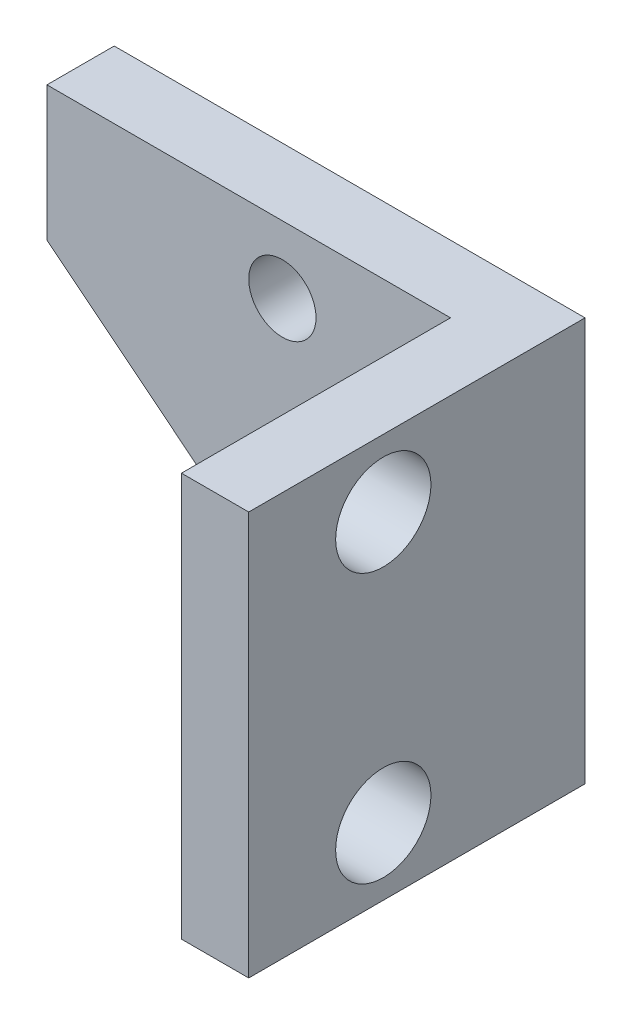
SolidWorks part; units mm, degrees
ref_plane "Front Plane" through (0, 0, 0) normal (0, 0, 1) x (1, 0, 0)
ref_plane "Top Plane" through (0, 0, 0) normal (0, 1, 0) x (1, 0, 0)
ref_plane "Right Plane" through (0, 0, 0) normal (1, 0, 0) x (0, 0, -1)
sketch "Sketch1" plane through (0, 0, 0) normal (0, 0, 1) x (1, 0, 0)
  line L0 (0, 0) -> (-22.225, 0)
  line L1 (-22.225, 0) -> (-22.225, -6.35)
  line L2 (-22.225, -6.35) -> (-6.35, -19.05)
  line L3 (-6.35, -19.05) -> (0, -19.05)
  line L4 (0, -19.05) -> (0, 0)
  dimension "D1" = 6.35
  dimension "D2" = 19.05
  dimension "D3" = 22.225
extrude "Boss-Extrude1" add sketch "Sketch1" along normal blind 3.175
hole_wizard "1/8 (0.1250) Dowel Hole2" positions "Sketch5" profile "Sketch6" hole size "1/8" standard "ANSI Inch" end condition through all
sketch "Sketch5" plane through (0, 0, 3.175) normal (0, 0, 1) x (1, 0, 0)
  line L0 (-22.225, -3.175) -> (0, -3.175) construction
  line L1 (-22.225, 0) -> (-22.225, -6.35) construction
  line L2 (0, -19.05) -> (0, 0) construction
  point P10 (-11.1125, -3.175)
sketch "Sketch6" plane through (-11.1125, -3.175, 3.175) normal (1, 0, 0) x (0, -1, 0)
  line L0 (0, 0) -> (0, 3.175)
  line L1 (0, 3.175) -> (1.5875, 3.175)
  line L2 (1.5875, 3.175) -> (1.5875, 0)
  line L5 (1.5875, 0) -> (0, 0)
  line L11 (0, -6.35) -> (0, 107.95) construction
  dimension "Thru Hole Dia." = 3.175
  dimension "Thru Hole Depth" = 3.175
sketch "Sketch7" plane through (0, 0, 3.175) normal (0, 0, 1) x (1, 0, 0)
  line L0 (-6.35, -19.05) -> (0, -19.05) construction
  line L1 (0, 0) -> (-3.175, 0)
  line L2 (0, 0) -> (0, -19.05)
  line L3 (0, -19.05) -> (-3.175, -19.05)
  line L4 (-3.175, 0) -> (-3.175, -19.05)
extrude "Boss-Extrude2" add sketch "Sketch7" along normal blind 15.875 from surface starting at face at (-9.525, -3.175, 0)
hole_wizard "#8 Clearance Hole1" positions "Sketch8" profile "Sketch9" hole size "#8" standard "ANSI Inch" end condition through all
sketch "Sketch8" plane through (-3.175, 0, 0) normal (-1, 0, 0) x (0, 0, 1)
  line L0 (9.525, 0) -> (9.525, -3.175) construction
  line L1 (15.875, 0) -> (3.175, 0) construction
  line L2 (9.525, -3.175) -> (9.525, -15.875) construction
  line L3 (9.525, -15.875) -> (9.525, -19.05) construction
  line L4 (15.875, -19.05) -> (3.175, -19.05) construction
  point P2 (9.525, -3.175)
  point P6 (9.525, -15.875)
  dimension "D1" = 3.175
sketch "Sketch9" plane through (-3.175, -15.875, 9.525) normal (0, 1, 0) x (0, 0, 1)
  line L0 (0, 0) -> (0, 3.175)
  line L1 (0, 3.175) -> (2.2479, 3.175)
  line L2 (2.2479, 3.175) -> (2.2479, 0)
  line L5 (2.2479, 0) -> (0, 0)
  line L11 (0, -6.35) -> (0, 107.95) construction
  dimension "Thru Hole Dia." = 4.4958
  dimension "Thru Hole Depth" = 3.175
